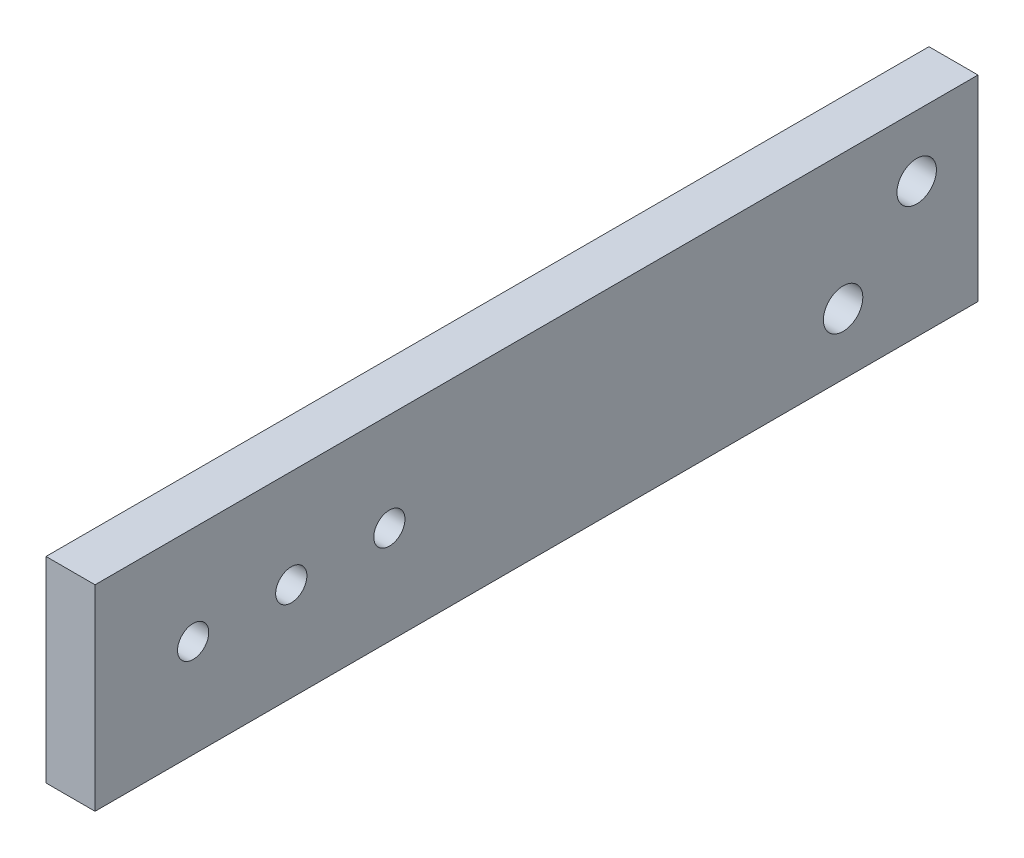
SolidWorks part; units mm, degrees
material "6061-T6 (SS)"
ref_plane "Front" through (0, 0, 0) normal (0, 0, 1) x (1, 0, 0)
ref_plane "Top" through (0, 0, 0) normal (0, 1, 0) x (1, 0, 0)
ref_plane "Right" through (0, 0, 0) normal (1, 0, 0) x (0, 0, -1)
sketch "Sketch1" plane through (0, 0, 0) normal (1, 0, 0) x (0, 0, -1)
  line L1 (0, 0) -> (114.3, 0)
  line L2 (0, 0) -> (0, 25.4)
  line L3 (0, 25.4) -> (114.3, 25.4)
  line L6 (114.3, 0) -> (114.3, 25.4)
  dimension "D1" = 25.4
  dimension "D4" = 114.3
extrude "Boss-Extrude1" add sketch "Sketch1" along normal blind 6.35
hole_wizard "#10-32 Tapped Hole1" positions "Sketch2" profile "Sketch3" tap size "#10-32" standard "ANSI Inch" end condition through all
sketch "Sketch2" plane through (6.35, 0, 0) normal (1, 0, 0) x (0, 0, -1)
  line L0 (0, 0) -> (12.7, 12.7) construction
  line L1 (12.7, 12.7) -> (25.4, 12.7) construction
  line L2 (25.4, 12.7) -> (38.1, 12.7) construction
  line L3 (38.1, 12.7) -> (50.8, 25.4) construction
  line L4 (114.3, 25.4) -> (0, 25.4) construction
  line L6 (0, 25.4) -> (0, 0) construction
  point P0 (12.7, 12.7)
  point P2 (25.4, 12.7)
  point P4 (38.1, 12.7)
  dimension "D1" = 50.8
  dimension "D2" = 12.7
sketch "Sketch3" plane through (6.35, 12.7, -12.7) normal (0, 1, 0) x (0, 0, -1)
  line L0 (0, 0) -> (0, 6.35)
  line L1 (0, 6.35) -> (2.0193, 6.35)
  line L2 (2.0193, 6.35) -> (2.0193, 0)
  line L5 (2.0193, 0) -> (0, 0)
  line L11 (0, -6.35) -> (0, 107.95) construction
  dimension "Thru Tap Drill Dia." = 4.0386
  dimension "Thru Tap Drill Depth" = 6.35
cosmetic thread "Hole Thread1" parameters "D2"=4.826
cosmetic thread "Hole Thread2" parameters "D2"=4.826
cosmetic thread "Hole Thread3" parameters "D2"=4.826
hole_wizard "#10 Clearance Hole1" positions "Sketch4" profile "Sketch5" hole size "#10" standard "ANSI Inch" end condition through all
sketch "Sketch4" plane through (6.35, 0, 0) normal (1, 0, 0) x (0, 0, -1)
  line L0 (88.9, 0) -> (96.8375, 7.9375) construction
  line L1 (0, 0) -> (114.3, 0) construction
  line L2 (96.8375, 7.9375) -> (106.3625, 17.4625) construction
  line L3 (106.3625, 17.4625) -> (114.3, 25.4) construction
  line L5 (114.3, 0) -> (114.3, 25.4) construction
  point P13 (106.3625, 17.4625)
  point P15 (96.8375, 7.9375)
  dimension "D1" = 25.4
  dimension "D2" = 9.525
sketch "Sketch5" plane through (6.35, 17.4625, -106.3625) normal (0, 1, 0) x (0, 0, -1)
  line L0 (0, 0) -> (0, 6.35)
  line L1 (0, 6.35) -> (2.5527, 6.35)
  line L2 (2.5527, 6.35) -> (2.5527, 0)
  line L5 (2.5527, 0) -> (0, 0)
  line L11 (0, -6.35) -> (0, 107.95) construction
  dimension "Thru Hole Dia." = 5.1054
  dimension "Thru Hole Depth" = 6.35
